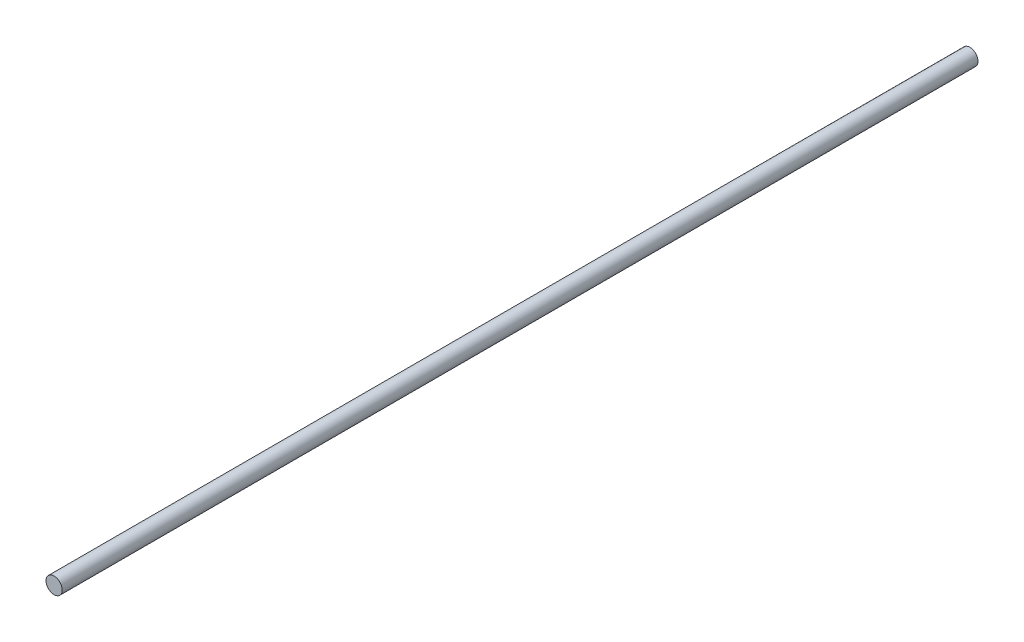
SolidWorks part; units mm, degrees
material "1023 Arkusz stali węglowej (SS)"
ref_plane "Płaszczyzna przednia" through (0, 0, 0) normal (0, 0, 1) x (1, 0, 0)
ref_plane "Płaszczyzna górna" through (0, 0, 0) normal (0, 1, 0) x (1, 0, 0)
ref_plane "Płaszczyzna prawa" through (0, 0, 0) normal (1, 0, 0) x (0, 0, -1)
sketch "Szkic1" plane through (0, 0, 0) normal (0, 0, 1) x (1, 0, 0)
  circle A0 centre (0, 0) radius 4
extrude "Dodanie-wyciągnięcie1" add sketch "Szkic1" along normal blind 452
